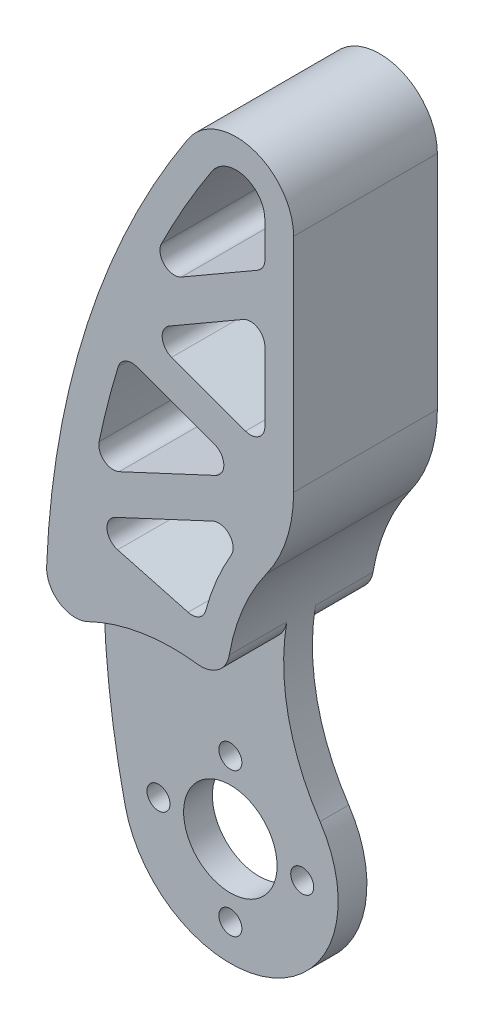
SolidWorks part; units mm, degrees
ref_plane "前视基准面" through (0, 0, 0) normal (0, 0, 1) x (1, 0, 0)
ref_plane "上视基准面" through (0, 0, 0) normal (0, 1, 0) x (1, 0, 0)
ref_plane "右视基准面" through (0, 0, 0) normal (1, 0, 0) x (0, 0, -1)
sketch "草图1" plane through (0, 0, 0) normal (0, 0, 1) x (1, 0, 0)
  circle A0 centre (0, 0) radius 6.5
  circle A1 centre (0, 0) radius 10 construction
  circle A2 centre (0, 0) radius 15
  circle A3 centre (0, 10) radius 1.6
  circle A4 centre (10, 0) radius 1.6
  circle A5 centre (0, -10) radius 1.6
  circle A6 centre (-10, 0) radius 1.6
  point P7 (-11.4284, -0.8393)
  point P8 (0, 0)
  point P16 (0, 0)
  dimension "D1" = 3.2
  dimension "D2" = 20
  dimension "D3" = 13
  dimension "D4" = 30
  dimension "D5" = 4
extrude "凸台-拉伸1" add sketch "草图1" along normal blind 4
sketch "草图2" plane through (0, 0, 4) normal (0, 0, 1) x (1, 0, 0)
  line L1 (16.8, 85) -> (16.8, 54.1598)
  arc A0 (-14.622, -3.3462) -> (2.1176, 89.3983) centre (102.354, 23.4236) cw
  circle A1 centre (0, 0) radius 15 construction
  arc A2 (12.4722, 8.3333) -> (13.0466, 42.4959) centre (37.4166, 25) cw
  arc A3 (12.4722, 8.3333) -> (-14.622, -3.3462) centre (0, 0) ccw
  arc A4 (2.1176, 89.3983) -> (16.8, 85) centre (8.8, 85) cw
  arc A5 (16.8, 54.1598) -> (13.0466, 42.4959) centre (-3.2, 54.1598) cw
  point P7 (13.8158, 5.8416)
  point P8 (10.3853, 30.8412)
  point P13 (13.5773, 6.3763)
  dimension "D1" = 8
  dimension "D4" = 30
  dimension "D5" = 120
  dimension "D6" = 20
  dimension "D2" = 85
  dimension "D3" = 16.8
  dimension "D7" = 25
extrude "凸台-拉伸3" add sketch "草图2" against normal up to surface (4 mm away) up to face at (15, 0, 0)
sketch "草图3" plane through (0, 0, 4) normal (0, 0, 1) x (1, 0, 0)
  line L1 (16.8, 54.1598) -> (16.8, 85)
  line L2 (16.8, 54.1598) -> (16.8, 85)
  arc A0 (-11.8108, 24.2797) -> (3.4027, 26.7847) centre (0, 0) cw
  arc A1 (2.1176, 89.3983) -> (-14.622, -3.3462) centre (102.354, 23.4236) ccw construction
  arc A2 (13.0466, 42.4959) -> (12.4722, 8.3333) centre (37.4166, 25) ccw construction
  circle A3 centre (0, 0) radius 6.5 construction
  arc A4 (3.4027, 26.7847) -> (7.8491, 30.076) centre (3.9068, 30.7528) ccw
  arc A5 (-11.8108, 24.2797) -> (-17.5576, 28.0303) centre (-13.5605, 27.8767) cw
  arc A9 (-14.622, -3.3462) -> (12.4722, 8.3333) centre (0, 0) ccw
  arc A10 (13.0466, 42.4959) -> (12.4722, 8.3333) centre (37.4166, 25) ccw
  arc A11 (13.0466, 42.4959) -> (16.8, 54.1598) centre (-3.2, 54.1598) ccw
  arc A12 (16.8, 85) -> (2.1176, 89.3983) centre (8.8, 85) ccw
  arc A13 (2.1176, 89.3983) -> (-14.622, -3.3462) centre (102.354, 23.4236) ccw
  arc A15 (13.0466, 42.4959) -> (7.8491, 30.076) centre (37.4166, 25) ccw
  arc A16 (13.0466, 42.4959) -> (16.8, 54.1598) centre (-3.2, 54.1598) ccw
  arc A17 (16.8, 85) -> (2.1176, 89.3983) centre (8.8, 85) ccw
  arc A18 (2.1176, 89.3983) -> (-17.5576, 28.0303) centre (102.354, 23.4236) ccw
  point P17 (7.4318, 25.957)
  point P27 (-17.6096, 20.4671)
  dimension "D1" = 27
  dimension "D3" = 4
  dimension "D2" = 0
extrude "凸台-拉伸4" add sketch "草图3" along normal blind 8 and the other way blind 12
sketch "草图5" plane through (0, 0, -8) normal (0, 0, -1) x (-1, 0, 0)
  line L0 (-12.8, 69.7624) -> (-12.8, 60.0828)
  line L1 (-11.8, 78.4226) -> (-1.2064, 72.3064)
  line L2 (-12.8, 85) -> (-12.8, 54.1598)
  line L3 (-12.8, 85) -> (-12.8, 80.1547)
  line L4 (-10.116, 58.2034) -> (0.167, 61.9461)
  line L5 (0.483, 65.5576) -> (-9.8, 71.4944)
  line L6 (5.0101, 58.3879) -> (-5.777, 54.4618)
  line L7 (-5.9382, 50.7698) -> (7.4531, 44.5253)
  line L8 (-2.1233, 32.3771) -> (7.682, 35.0045)
  line L9 (8.0096, 38.7489) -> (-5.5439, 45.069)
  arc A0 (7.6065, 57.0941) -> (10.2568, 46.7435) centre (-102.354, 23.4236) cw
  arc A1 (17.5576, 28.0303) -> (-2.1176, 89.3983) centre (-102.354, 23.4236) ccw construction
  arc A2 (-8.1128, 42.2421) -> (-4.5729, 33.7918) centre (-37.4166, 25) cw
  arc A3 (-7.8491, 30.076) -> (-13.0466, 42.4959) centre (-37.4166, 25) ccw construction
  arc A4 (7.682, 35.0045) -> (8.0096, 38.7489) centre (7.1643, 36.9363) ccw
  arc A5 (-5.777, 54.4618) -> (-5.9382, 50.7698) centre (-5.093, 52.5824) ccw
  arc A6 (-4.5729, 33.7918) -> (-2.1233, 32.3771) centre (-2.641, 34.309) ccw
  arc A7 (10.2568, 46.7435) -> (7.4531, 44.5253) centre (8.2983, 46.3379) cw
  arc A8 (-8.1128, 42.2421) -> (-5.5439, 45.069) centre (-6.3891, 43.2564) cw
  arc A9 (0.167, 61.9461) -> (0.483, 65.5576) centre (-0.517, 63.8255) ccw
  arc A10 (7.6065, 57.0941) -> (5.0101, 58.3879) centre (5.6941, 56.5086) ccw
  arc A11 (-12.8, 60.0828) -> (-10.116, 58.2034) centre (-10.8, 60.0828) ccw
  arc A12 (-12.8, 69.7624) -> (-9.8, 71.4944) centre (-10.8, 69.7624) cw
  arc A13 (-1.2064, 72.3064) -> (1.5857, 74.9264) centre (-0.2064, 74.0385) ccw
  arc A14 (13.5605, 27.8767) -> (-3.9068, 30.7528) centre (0, 0) ccw
  arc A15 (13.5605, 27.8767) -> (-5.4588, 87.1992) centre (-102.354, 23.4236) ccw
  arc A16 (-5.4588, 87.1992) -> (-12.8, 85) centre (-8.8, 85) ccw
  arc A17 (-12.8, 54.1598) -> (-9.7973, 44.8287) centre (3.2, 54.1598) ccw
  arc A18 (-3.9068, 30.7528) -> (-9.7973, 44.8287) centre (-37.4166, 25) ccw
  arc A20 (1.5857, 74.9264) -> (-5.4588, 87.1992) centre (-102.354, 23.4236) ccw
  arc A21 (-5.4588, 87.1992) -> (-12.8, 85) centre (-8.8, 85) ccw
  arc A22 (-11.8, 78.4226) -> (-12.8, 80.1547) centre (-10.8, 80.1547) cw
  point P12 (0, 0)
  point P19 (-11.738, 52.9784)
  point P20 (4.3768, 68.8136)
  point P24 (-12.4401, 48.069)
  point P26 (0, 0)
  point P39 (-4.1126, 31.8441)
  point P44 (-12.8, 48.4526)
  point P51 (-12.8, 57.2265)
  point P54 (-12.8, 73.2265)
  point P59 (-12.8, 79)
  dimension "D3" = 5
  dimension "D4" = 4
  dimension "D14" = 2
  dimension "D2" = 5
  dimension "D5" = 5
  dimension "D6" = 5
  dimension "D7" = 120
  dimension "D8" = 6
  dimension "D9" = 50
  dimension "D10" = 16
  dimension "D11" = 45
  dimension "D12" = 32
  dimension "D13" = 40
  dimension "D1" = 4
extrude "切除-拉伸1" cut sketch "草图5" against normal blind 46
